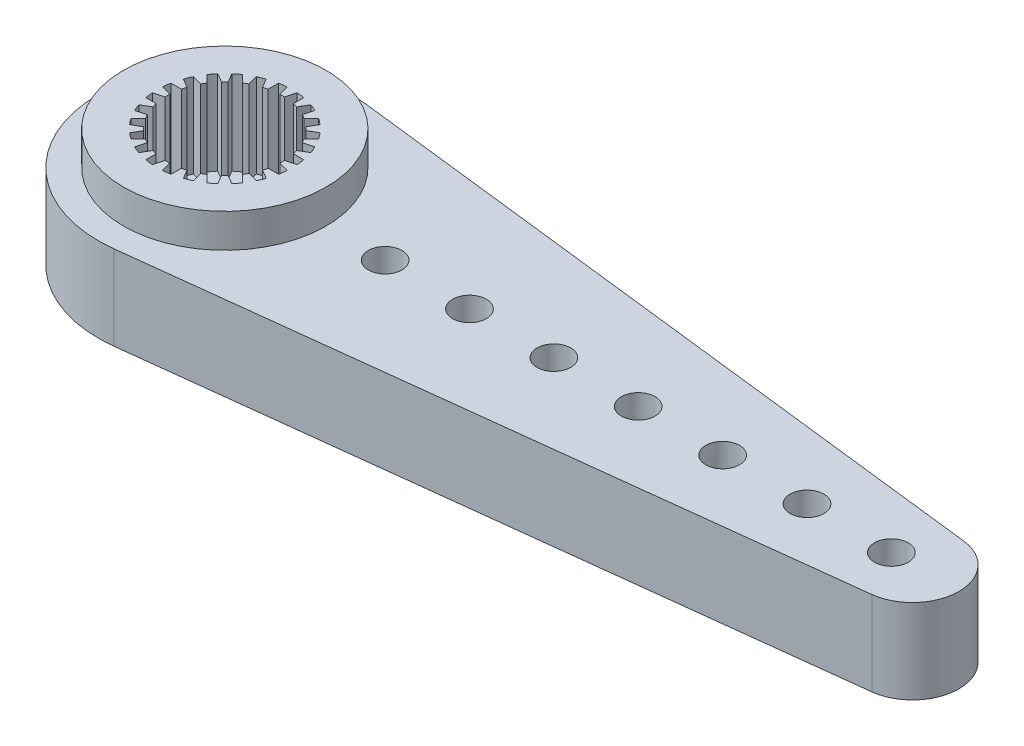
SolidWorks part; units mm, degrees
ref_plane "Plan de face" through (0, 0, 0) normal (0, 0, 1) x (1, 0, 0)
ref_plane "Plan de dessus" through (0, 0, 0) normal (0, 1, 0) x (1, 0, 0)
ref_plane "Plan de droite" through (0, 0, 0) normal (1, 0, 0) x (0, 0, -1)
sketch "Esquisse1" plane through (0, 0, 0) normal (0, 1, 0) x (1, 0, 0)
  line L0 (0.8742, -7.4489) -> (41.0706, -2.7313)
  line L1 (41.0706, 2.7313) -> (0.8742, 7.4489)
  line L2 (-7.5, 27.3999) -> (-7.5, -15.4168) construction
  line L3 (-7.5, -15.4168) -> (43.5, -15.4168) construction
  line L4 (43.5, -15.4168) -> (43.5, 24.8813) construction
  arc A0 (0.8742, 7.4489) -> (0.8742, -7.4489) centre (0, 0) ccw
  arc A1 (41.0706, -2.7313) -> (41.0706, 2.7313) centre (40.75, 0) ccw
  circle A2 centre (0, 0) radius 1.6
  dimension "D1" = 2.75
  dimension "D2" = 7.5
  dimension "D4" = 3.2
  dimension "D3" = 51
extrude "Boss.-Extru.1" add sketch "Esquisse1" along normal blind 8
sketch "Esquisse2" plane through (0, 8, 0) normal (0, 1, 0) x (1, 0, 0)
  line L0 (0, 0) -> (46.1588, 0) construction
  line L1 (-7.5, 15.192) -> (-7.5, -12.3349) construction
  circle A0 centre (9.5, 0) radius 1
  arc A1 (0.8742, 7.4489) -> (0.8742, -7.4489) centre (0, 0) ccw construction
  dimension "D1" = 2
  dimension "D2" = 17
extrude "Enlèv. mat.-Extru.1" cut sketch "Esquisse2" against normal blind 8
pattern_linear "Répétition linéaire1" count 7 spacing 5 along (1, 0, 0) of "Enlèv. mat.-Extru.1"
sketch "Esquisse3" plane through (0, 8, 0) normal (0, 1, 0) x (1, 0, 0)
  line L1 (-12.783, 10.2172) -> (50.2427, 10.2172)
  line L2 (-12.783, 10.2172) -> (-12.783, -12.2303)
  line L3 (-12.783, -12.2303) -> (50.2427, -12.2303)
  line L4 (50.2427, 10.2172) -> (50.2427, -12.2303)
  circle A0 centre (0, 0) radius 6
  dimension "D1" = 12
extrude "Enlèv. mat.-Extru.2" cut sketch "Esquisse3" against normal blind 2
sketch "Esquisse4" plane through (0, 0, 0) normal (0, -1, 0) x (1, 0, 0)
  line L1 (-13.4769, 12.3588) -> (51.6733, 12.3588)
  line L2 (-13.4769, 12.3588) -> (-13.4769, -11.2271)
  line L3 (-13.4769, -11.2271) -> (51.6733, -11.2271)
  line L4 (51.6733, 12.3588) -> (51.6733, -11.2271)
  circle A0 centre (0, 0) radius 4.65
  dimension "D1" = 9.3
extrude "Enlèv. mat.-Extru.3" cut sketch "Esquisse4" against normal blind 1
sketch "Esquisse5" plane through (0, 0, 0) normal (0, -1, 0) x (1, 0, 0)
  circle A0 centre (0, 0) radius 2.75
  dimension "D1" = 5.5
extrude "Enlèv. mat.-Extru.4" cut sketch "Esquisse5" against normal blind 1
chamfer "Chanfrein1" distance 1 angle 45 1 edges at (0, 1, -4.65)
sketch "Esquisse6" plane through (0, 8, 0) normal (0, 1, 0) x (1, 0, 0)
  circle A0 centre (0, 0) radius 4
  dimension "D1" = 8
extrude "Enlèv. mat.-Extru.5" cut sketch "Esquisse6" against normal blind 5
sketch "Esquisse7" plane through (0, 8, 0) normal (0, 1, 0) x (1, 0, 0)
  line L0 (0, 0) -> (0, -6.8034) construction
  line L1 (0, -6.8034) -> (2.7804, -4) construction
  line L2 (2.7804, -4) -> (-2.8896, -4) construction
  line L3 (0.3, -4) -> (0.1392, -3.4)
  line L4 (0.1392, -3.4) -> (-0.1392, -3.4)
  line L5 (-0.1392, -3.4) -> (-0.3, -4)
  line L6 (-0.3, -4) -> (0.3, -4)
  circle A0 centre (0, 0) radius 4 construction
  dimension "D1" = 0.6
  dimension "D2" = 0.6
  dimension "D3" = 15
extrude "Boss.-Extru.2" add sketch "Esquisse7" against normal up to surface (5 mm away) up to face at (0, 3, 1.6)
pattern_circular "Répétition circulaire1" count 24 over 360 about axis through (0, 8, 0) along (0, -1, 0) of "Boss.-Extru.2"
